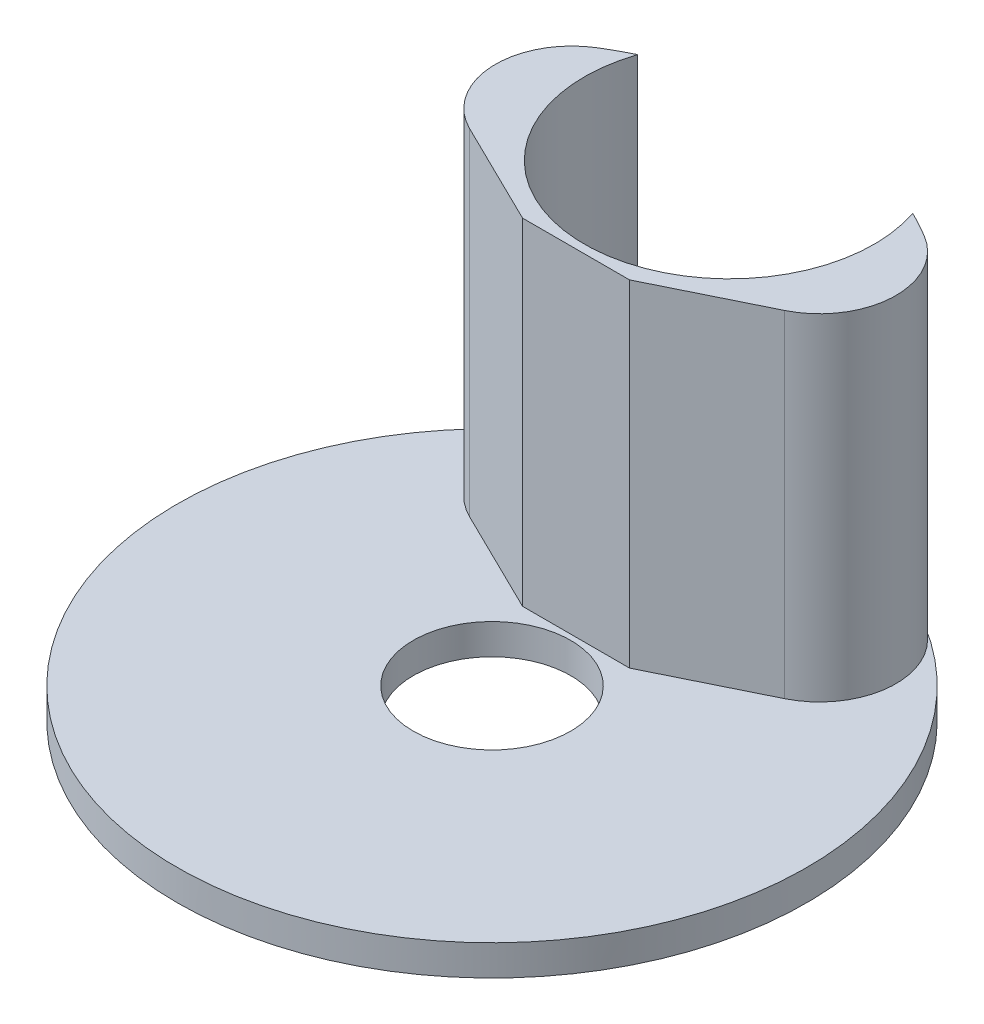
SolidWorks part; units mm, degrees
ref_plane "Front Plane" through (0, 0, 0) normal (0, 0, 1) x (1, 0, 0)
ref_plane "Top Plane" through (0, 0, 0) normal (0, 1, 0) x (1, 0, 0)
ref_plane "Right Plane" through (0, 0, 0) normal (1, 0, 0) x (0, 0, -1)
sketch "Sketch1" plane through (0, 0, 0) normal (0, 1, 0) x (1, 0, 0)
  circle A0 centre (0, 0) radius 20.6
  dimension "D1" = 41.2
extrude "Boss-Extrude1" add sketch "Sketch1" along normal blind 2
sketch "Sketch2" plane through (0, 2, 0) normal (0, 1, 0) x (1, 0, 0)
  circle A0 centre (0, 0) radius 5.15
  dimension "D1" = 10.3
extrude "Cut-Extrude1" cut sketch "Sketch2" against normal blind 3
sketch "Sketch3" plane through (0, 2, 0) normal (0, 1, 0) x (1, 0, 0)
  circle A0 centre (0, 13) radius 6.5
  dimension "D2" = 13
  dimension "D1" = 13
extrude "Cut-Extrude2" cut sketch "Sketch3" against normal blind 2
sketch "Sketch4" plane through (0, 2, 0) normal (0, 1, 0) x (1, 0, 0)
  line L0 (-3.5, 5.5) -> (-16.744, 12)
  line L1 (3.5, 5.5) -> (16.744, 12)
  line L4 (-3.5, 5.5) -> (3.5, 5.5)
  arc A0 (-16.744, 12) -> (-9, 18.53) centre (0, 0) cw
  circle A1 centre (0, 0) radius 20.6 construction
  arc A4 (9, 18.53) -> (16.744, 12) centre (0, 0) cw
  arc A6 (-9, 18.53) -> (9, 18.53) centre (0, 15.5297) ccw
  dimension "D1" = 12
  dimension "D2" = 12
  dimension "D3" = 5.5
  dimension "D4" = 5.5
  dimension "D5" = 3.5
  dimension "D6" = 3.5
  dimension "D7" = 9
  dimension "D8" = 9
extrude "Boss-Extrude4" add sketch "Sketch4" along normal blind 22
fillet "Fillet2" radius 5 2 edges at (16.744, 13, -12) (-16.744, 13, -12)
